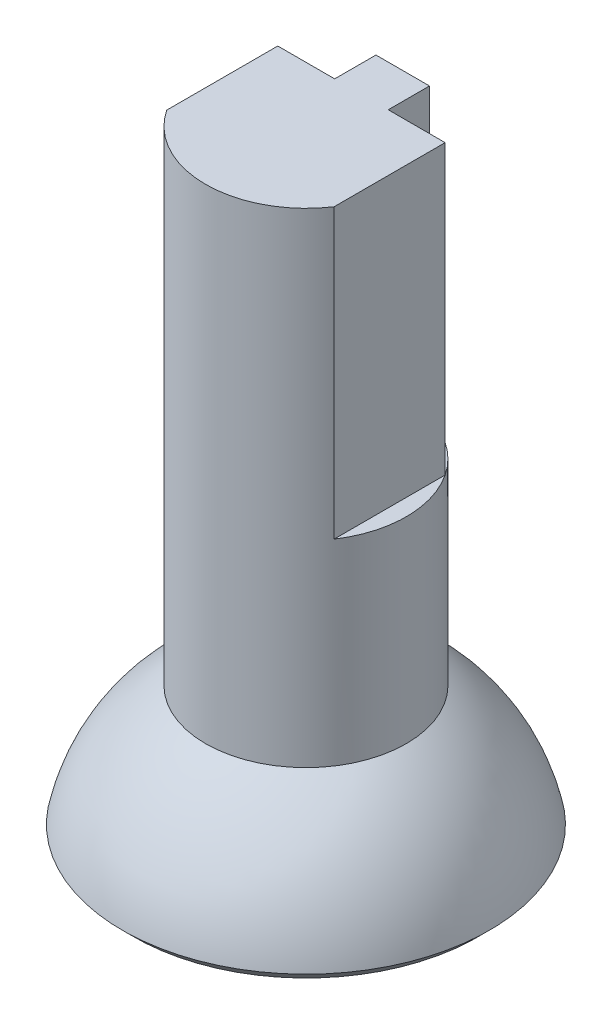
SolidWorks part; units mm, degrees
ref_plane "Front Plane" through (0, 0, 0) normal (0, 0, 1) x (1, 0, 0)
ref_plane "Top Plane" through (0, 0, 0) normal (0, 1, 0) x (1, 0, 0)
ref_plane "Right Plane" through (0, 0, 0) normal (1, 0, 0) x (0, 0, -1)
sketch "Sketch3" plane through (0, 0, 0) normal (0, 0, 1) x (1, 0, 0)
  line L0 (0, 0) -> (0, 12.192) construction
  line L2 (-1.905, 12.192) -> (-1.905, 3.0027)
  line L3 (-3.556, 0) -> (-2.54, 0)
  line L4 (0, 0) -> (-4.2652, 0) construction
  line L7 (-1.27, 2.1997) -> (0, 2.9329)
  line L8 (-1.27, 2.1997) -> (-1.27, 3.6416) construction
  line L9 (-1.905, 12.192) -> (0, 12.192)
  line L11 (0, 12.192) -> (0, 2.9329)
  line L12 (-3.5195, 0.508) -> (-2.4887, 0.508)
  line L13 (-3.556, 0) -> (-3.556, -0.508)
  line L17 (-3.556, -0.508) -> (-3.2262, -0.508)
  line L18 (-2.1997, 1.27) -> (-3.6759, -1.2869) construction
  line L19 (-3.2262, -0.508) -> (-2.1997, 1.27)
  arc A2 (-1.905, 3.0027) -> (-3.556, 0) centre (0, 0) ccw
  arc A5 (-2.54, 0) -> (-1.27, 2.1997) centre (0, 0) cw
  circle A6 centre (0, 0) radius 2.54 construction
  dimension "D1" = 2.54
  dimension "D2" = 12.192
  dimension "D3" = 1.905
  dimension "D5" = 1.016
  dimension "D4" = 60
  dimension "D6" = 0.508
  dimension "D8" = 0.508
revolve "Revolve1" add sketch "Sketch3" angle 360 about L11 region at (-1.1449, 6.6719, 0)
sketch "Sketch4" plane through (0, 12.192, 0) normal (0, 1, 0) x (1, 0, 0)
  line L0 (0, -1.905) -> (0, 1.905) construction
  line L1 (3.1721, -1.905) -> (1.5875, -1.905)
  line L2 (-3.1721, 1.905) -> (-1.5875, 1.905)
  line L3 (-3.1721, 1.905) -> (-3.1721, -1.905)
  line L4 (-3.1721, -1.905) -> (-1.5875, -1.905)
  line L5 (-1.5875, 1.905) -> (-1.5875, -1.905)
  line L6 (3.1721, 1.905) -> (3.1721, -1.905)
  line L7 (3.1721, 1.905) -> (1.5875, 1.905)
  line L8 (1.5875, 1.905) -> (1.5875, -1.905)
  line L10 (-0.508, 1.836) -> (0.508, 1.836)
  line L11 (-0.508, 1.836) -> (-0.508, 1.053)
  line L12 (-0.508, 1.053) -> (0.508, 1.053)
  line L13 (0.508, 1.836) -> (0.508, 1.053)
  line L14 (-0.508, 1.836) -> (0.508, 1.053) construction
  line L15 (-0.508, 1.053) -> (0.508, 1.836) construction
  line L16 (-0.508, 1.053) -> (-1.5875, 1.053)
  line L17 (-0.508, 1.053) -> (-0.508, 1.905)
  line L18 (-0.508, 1.905) -> (-1.5875, 1.905)
  line L19 (-1.5875, 1.053) -> (-1.5875, 1.905)
  line L20 (0.508, 1.053) -> (1.5875, 1.053)
  line L21 (0.508, 1.053) -> (0.508, 1.905)
  line L22 (0.508, 1.905) -> (1.5875, 1.905)
  line L23 (1.5875, 1.053) -> (1.5875, 1.905)
  line L24 (-1.5875, 3.0703) -> (1.5875, 3.0703)
  line L25 (-1.5875, 3.0703) -> (-1.5875, 1.836)
  line L26 (-1.5875, 1.836) -> (1.5875, 1.836)
  line L27 (1.5875, 3.0703) -> (1.5875, 1.836)
  circle A0 centre (0, 0) radius 1.905 construction
  circle A1 centre (0, 0) radius 1.905 construction
  point P15 (0, 1.4445)
  circle M7 centre (0, 0) radius 1.905
  dimension "D1" = 3.175
  dimension "D2" = 1.016
extrude "Cut-Extrude1" cut sketch "Sketch4" against normal blind 5.461 contours L5 L2 L3 L4 L19 M7 | L16 L11 L5 M7 | L26 L19 M7 | L27 L24 L25 L18 L17 L21 L22 M7 | L5 L26 L17 L18 | L10 M7 | L21 L26 L8 L22 | L26 L23 M7 | L13 L20 L8 M7 | L7 L8 L23 L1 L6 M7 | L8 M7 | L5 M7 region at (2.4338, 12.192, 0) region at (1.7155, 12.192, 0) region at (1.0477, 12.192, -1.8705) region at (0, 12.192, -2.4839) region at (1.2796, 12.192, -1.6063) region at (0.9102, 12.192, -1.3485) region at (-1.7155, 12.192, 0) region at (-2.4338, 12.192, 0) region at (0, 12.192, -1.8637) region at (-0.9102, 12.192, -1.3485) region at (-1.2796, 12.192, -1.6063) region at (-1.0478, 12.192, -1.8705)
chamfer "Chamfer1" distance 0.254 angle 45 1 edges at (-3.5195, 0.508, 0) first distance on face at (-2.6396, 0.508, 0)
